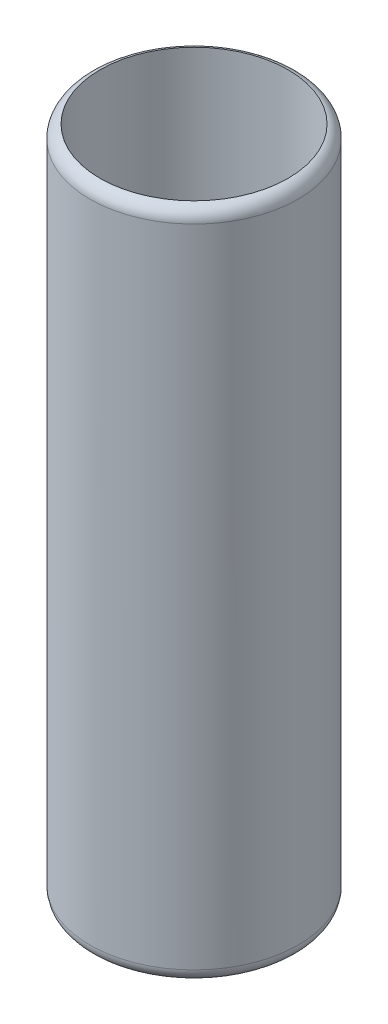
SolidWorks part; units mm, degrees
ref_plane "前视基准面" through (0, 0, 0) normal (0, 0, 1) x (1, 0, 0)
ref_plane "上视基准面" through (0, 0, 0) normal (0, 1, 0) x (1, 0, 0)
ref_plane "右视基准面" through (0, 0, 0) normal (1, 0, 0) x (0, 0, -1)
sketch "草图1" plane through (0, 0, 0) normal (0, 1, 0) x (1, 0, 0)
  circle A0 centre (0, 0) radius 15.5
  circle A1 centre (0, 0) radius 14
  dimension "D1" = 31
  dimension "D2" = 28
extrude "凸台-拉伸1" add sketch "草图1" along normal blind 100
cosmetic thread "装饰螺纹线1" parameters "D2"=26.211
fillet "圆角1" radius 2 2 edges at (0, 0, 15.5) (0, 100, 15.5)
